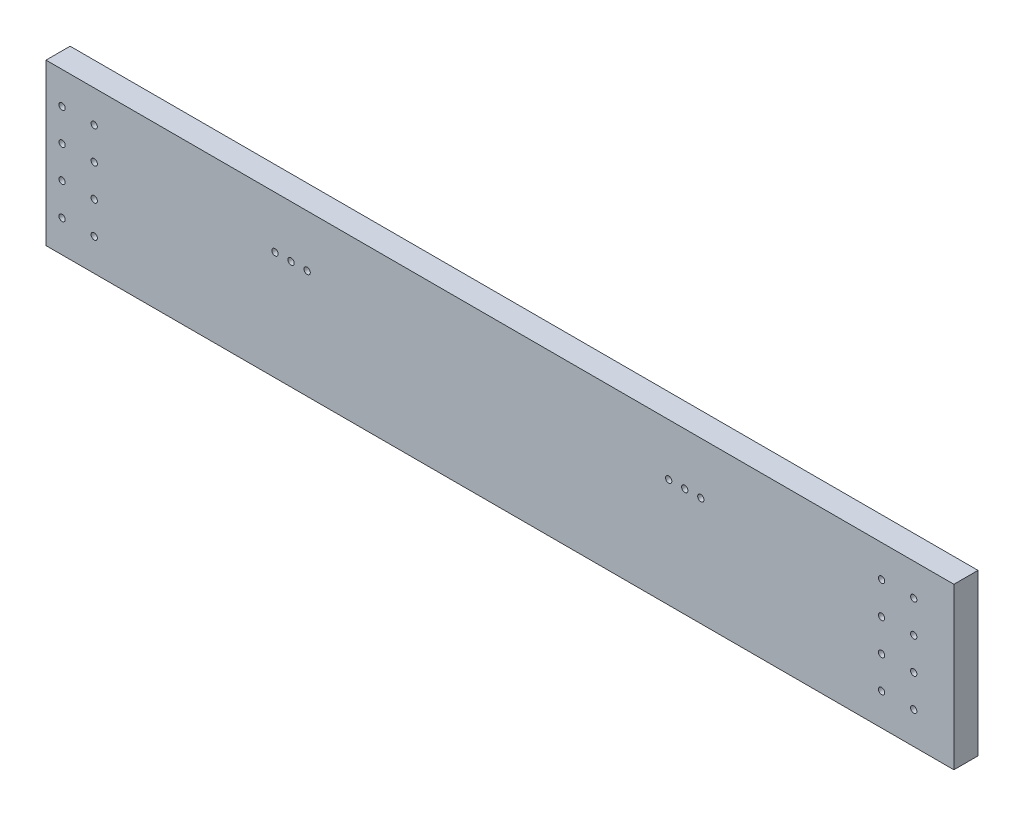
SolidWorks part; units mm, degrees
material "Pine"
ref_plane "Front Plane" through (0, 0, 0) normal (0, 0, 1) x (1, 0, 0)
ref_plane "Top Plane" through (0, 0, 0) normal (0, 1, 0) x (1, 0, 0)
ref_plane "Right Plane" through (0, 0, 0) normal (1, 0, 0) x (0, 0, -1)
sketch "Sketch1" plane through (0, 0, 0) normal (0, 0, 1) x (1, 0, 0)
  line L1 (0, 0) -> (717.55, 0)
  line L2 (0, 0) -> (0, 127)
  line L3 (0, 127) -> (717.55, 127)
  line L4 (717.55, 0) -> (717.55, 127)
  line L6 (717.55, 0) -> (717.55, 127)
  line L9 (0, 127) -> (-19.05, 127)
  line L10 (0, 127) -> (0, 0)
  line L11 (0, 0) -> (-19.05, 0)
  line L12 (-19.05, 127) -> (-19.05, 0)
  dimension "D1" = 717.55
  dimension "D2" = 127
  dimension "D3" = 19.05
extrude "Boss-Extrude1" add sketch "Sketch1" along normal blind 19.05 contours L1 L4 L3 L2 region at (358.775, 63.5, 0)
sketch "Sketch2" plane through (0, 0, 19.05) normal (0, 0, 1) x (1, 0, 0)
  line L3 (0, 0) -> (0, 127) construction
  line L4 (0, 127) -> (717.55, 127) construction
  line L5 (717.55, 0) -> (717.55, 127) construction
  circle A0 centre (12.7, 101.6) radius 2.4892
  circle A1 centre (38.1, 101.6) radius 2.4892
  circle A2 centre (38.1, 76.2) radius 2.4892
  circle A3 centre (38.1, 50.8) radius 2.4892
  circle A4 centre (38.1, 25.4) radius 2.4892
  circle A5 centre (12.7, 76.2) radius 2.4892
  circle A6 centre (12.7, 50.8) radius 2.4892
  circle A7 centre (12.7, 25.4) radius 2.4892
  circle A8 centre (685.8, 101.6) radius 2.4892
  circle A9 centre (660.4, 101.6) radius 2.4892
  circle A10 centre (660.4, 76.2) radius 2.4892
  circle A11 centre (660.4, 50.8) radius 2.4892
  circle A12 centre (660.4, 25.4) radius 2.4892
  circle A13 centre (685.8, 76.2) radius 2.4892
  circle A14 centre (685.8, 50.8) radius 2.4892
  circle A15 centre (685.8, 25.4) radius 2.4892
  dimension "D1" = 4.9784
  dimension "D2" = 25.4
  dimension "D3" = 12.7
  dimension "D6" = 25.4
  dimension "D7" = 31.75
  dimension "D8" = 4.9784
  dimension "D11" = 25.4
  dimension "D12" = 25.4
  dimension "D13" = 25.4
  dimension "D14" = 25.4
  dimension "D4" = 2
  dimension "D5" = 4
  dimension "D9" = 2
  dimension "D10" = 4
extrude "Cut-Extrude1" cut sketch "Sketch2" against normal blind 25.4
sketch "Sketch4" plane through (0, 0, 19.05) normal (0, 0, 1) x (1, 0, 0)
  line L0 (180.975, 85.979) -> (206.375, 85.979) construction
  line L1 (0, 127) -> (717.55, 127) construction
  line L2 (492.125, 85.979) -> (517.525, 85.979) construction
  line L3 (206.375, 85.979) -> (492.125, 85.979) construction
  line L4 (-19.05, 127) -> (717.55, 127) construction
  line L5 (-19.05, 127) -> (-19.05, 0) construction
  circle A0 centre (180.975, 85.979) radius 2.4892
  circle A1 centre (193.675, 85.979) radius 2.4892
  circle A2 centre (206.375, 85.979) radius 2.4892
  circle A3 centre (492.125, 85.979) radius 2.4892
  circle A4 centre (504.825, 85.979) radius 2.4892
  circle A5 centre (517.525, 85.979) radius 2.4892
  point P19 (0, 0)
  point P21 (349.25, 127)
  point P22 (349.25, 85.979)
  dimension "D1" = 4.9784
  dimension "D2" = 41.021
  dimension "D4" = 4.9784
  dimension "D6" = 41.021
  dimension "D7" = 285.75
  dimension "D3" = 12.7
  dimension "D5" = 12.7
extrude "Cut-Extrude2" cut sketch "Sketch4" against normal through all
